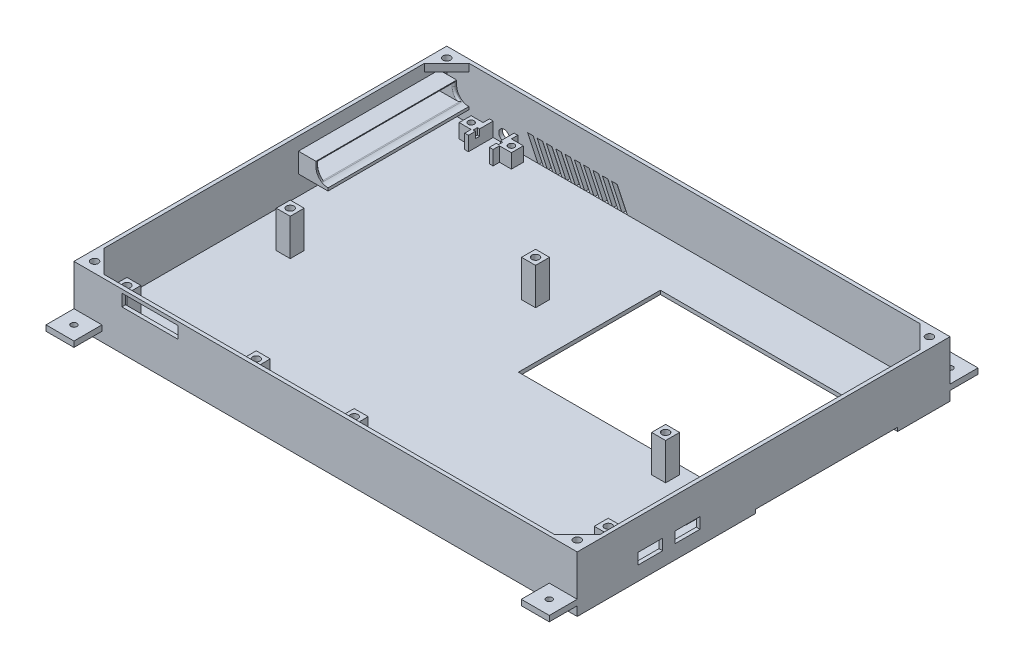
SolidWorks part; units mm, degrees
material "PLA"
ref_plane "Спереди" through (0, 0, 0) normal (0, 0, 1) x (1, 0, 0)
ref_plane "Сверху" through (0, 0, 0) normal (0, 1, 0) x (1, 0, 0)
ref_plane "Справа" through (0, 0, 0) normal (1, 0, 0) x (0, 0, -1)
sketch "Эскиз1" plane through (0, 0, 0) normal (0, 1, 0) x (1, 0, 0)
  line L1 (135, 100) -> (-135, 100)
  line L2 (135, 100) -> (135, -100)
  line L3 (135, -100) -> (-135, -100)
  line L4 (-135, 100) -> (-135, -100)
  line L5 (135, 100) -> (-135, -100) construction
  line L6 (135, -100) -> (-135, 100) construction
  point P0 (0, 0)
  dimension "D1" = 200
  dimension "D2" = 270
extrude "Бобышка-Вытянуть1" add sketch "Эскиз1" along normal blind 2
sketch "Эскиз2" plane through (0, 2, 0) normal (0, 1, 0) x (1, 0, 0)
  line L0 (133, 98) -> (-133, 98)
  line L1 (-133, 98) -> (-133, -98)
  line L2 (-133, -98) -> (-109.3, -98)
  line L3 (133, -98) -> (133, 98)
  line L4 (-135, 100) -> (-135, -100)
  line L5 (-135, -100) -> (135, -100)
  line L6 (135, -100) -> (135, 100)
  line L7 (135, 100) -> (-135, 100)
  line L8 (-135, 100) -> (-135, -100)
  line L9 (-135, -100) -> (-109.3, -100)
  line L10 (135, -100) -> (135, 100)
  line L11 (135, 100) -> (-135, 100)
  line L12 (-109.3, -98) -> (-109.3, -100)
  line L14 (-79.1, -98) -> (-79.1, -100)
  line L16 (-79.1, -98) -> (133, -98)
  line L17 (-79.1, -100) -> (135, -100)
  line L18 (-133, -98) -> (133, -98) construction
  line L20 (-135, -100) -> (135, -100) construction
  dimension "D3" = 25.7
  dimension "D4" = 55.9
  dimension "D1" = 0
  dimension "D2" = 2
extrude "Бобышка-Вытянуть2" add sketch "Эскиз2" along normal offset from surface (28 mm away) 7 offset beyond the face yes
sketch "Эскиз3" plane through (0, 2, 0) normal (0, 1, 0) x (1, 0, 0)
  line L1 (-109.3, -98) -> (-79.1, -98)
  line L2 (-109.3, -98) -> (-109.3, -100)
  line L3 (-109.3, -100) -> (-79.1, -100)
  line L4 (-79.1, -98) -> (-79.1, -100)
extrude "Бобышка-Вытянуть3" add sketch "Эскиз3" along normal blind 19.7
sketch "Эскиз4" plane through (-109.3, 0, 0) normal (1, 0, 0) x (0, 0, -1)
  line L0 (-100, 30) -> (-100, 21.7) construction
  line L1 (-98, 30) -> (-100, 30)
  line L2 (-98, 30) -> (-98, 28.1)
  line L3 (-98, 28.1) -> (-100, 28.1)
  line L4 (-100, 30) -> (-100, 28.1)
  dimension "D1" = 1.9
extrude "Бобышка-Вытянуть4" add sketch "Эскиз4" along normal up to surface (30.2 mm away) up to face at (-79.1, 25.85, 99)
sketch "Эскиз5" plane through (135, 0, 0) normal (1, 0, 0) x (0, 0, -1)
  line L0 (-100, 30) -> (-100, 0) construction
  line L1 (-54.15, 13.5) -> (-67.45, 13.5)
  line L2 (-54.15, 13.5) -> (-54.15, 7.6)
  line L3 (-54.15, 7.6) -> (-67.45, 7.6)
  line L4 (-67.45, 13.5) -> (-67.45, 7.6)
  line L5 (-54.15, 13.5) -> (-67.45, 7.6) construction
  line L6 (-54.15, 7.6) -> (-67.45, 13.5) construction
  line L7 (-34.15, 13.5) -> (-47.45, 13.5)
  line L8 (-34.15, 13.5) -> (-34.15, 7.6)
  line L9 (-34.15, 7.6) -> (-47.45, 7.6)
  line L10 (-47.45, 13.5) -> (-47.45, 7.6)
  line L11 (-34.15, 13.5) -> (-47.45, 7.6) construction
  line L12 (-34.15, 7.6) -> (-47.45, 13.5) construction
  line L13 (-100, 0) -> (100, 0) construction
  point P0 (-60.8, 10.55)
  point P5 (-40.8, 10.55)
  dimension "D1" = 13.3
  dimension "D2" = 5.9
  dimension "D3" = 6.7
  dimension "D4" = 32.55
  dimension "D5" = 13.5
extrude "Вырез-Вытянуть1" cut sketch "Эскиз5" against normal up to surface (2 mm away) up to face at (133, 16, 0)
sketch "Эскиз10" plane through (0, 2, 0) normal (0, 1, 0) x (1, 0, 0)
  line L0 (133, 98) -> (133, -98) construction
  line L1 (123.675, -22.825) -> (116.175, -22.825)
  line L2 (123.675, -22.825) -> (123.675, -30.325)
  line L3 (123.675, -30.325) -> (116.175, -30.325)
  line L4 (116.175, -22.825) -> (116.175, -30.325)
  line L5 (123.675, -22.825) -> (116.175, -30.325) construction
  line L6 (123.675, -30.325) -> (116.175, -22.825) construction
  line L7 (114.05, -54.9) -> (106.55, -54.9)
  line L8 (114.05, -54.9) -> (114.05, -62.4)
  line L9 (114.05, -62.4) -> (106.55, -62.4)
  line L10 (106.55, -54.9) -> (106.55, -62.4)
  line L11 (114.05, -54.9) -> (106.55, -62.4) construction
  line L12 (114.05, -62.4) -> (106.55, -54.9) construction
  line L13 (114.675, -87.875) -> (107.175, -87.875)
  line L14 (114.675, -87.875) -> (114.675, -95.375)
  line L15 (114.675, -95.375) -> (107.175, -95.375)
  line L16 (107.175, -87.875) -> (107.175, -95.375)
  line L17 (114.675, -87.875) -> (107.175, -95.375) construction
  line L18 (114.675, -95.375) -> (107.175, -87.875) construction
  line L19 (133, -98) -> (-133, -98) construction
  point P0 (119.925, -26.575)
  point P5 (110.3, -58.65)
  point P10 (110.925, -91.625)
  dimension "D1" = 13.075
  dimension "D2" = 71.425
  dimension "D3" = 22.7
  dimension "D4" = 39.35
  dimension "D5" = 22.075
  dimension "D6" = 6.375
  dimension "D7" = 7.5
extrude "Бобышка-Вытянуть6" add sketch "Эскиз10" along normal blind 6.9
sketch "Эскиз11" plane through (0, 2, 0) normal (0, 1, 0) x (1, 0, 0)
  line L1 (-45.3446, -84.35) -> (-52.8446, -84.35)
  line L2 (-45.3446, -84.35) -> (-45.3446, -91.85)
  line L3 (-45.3446, -91.85) -> (-52.8446, -91.85)
  line L4 (-52.8446, -84.35) -> (-52.8446, -91.85)
  line L5 (-45.3446, -84.35) -> (-52.8446, -91.85) construction
  line L6 (-45.3446, -91.85) -> (-52.8446, -84.35) construction
  line L7 (-17.6224, 30.2491) -> (-25.1224, 30.2491)
  line L8 (-17.6224, 30.2491) -> (-17.6224, 37.7491)
  line L9 (-17.6224, 37.7491) -> (-25.1224, 37.7491)
  line L10 (-25.1224, 30.2491) -> (-25.1224, 37.7491)
  line L11 (-17.6224, 30.2491) -> (-25.1224, 37.7491) construction
  line L12 (-17.6224, 37.7491) -> (-25.1224, 30.2491) construction
  line L13 (-114.1446, -92.4424) -> (-121.6446, -92.4424)
  line L14 (-114.1446, -92.4424) -> (-114.1446, -84.9424)
  line L15 (-114.1446, -84.9424) -> (-121.6446, -84.9424)
  line L16 (-121.6446, -92.4424) -> (-121.6446, -84.9424)
  line L17 (-114.1446, -92.4424) -> (-121.6446, -84.9424) construction
  line L18 (-114.1446, -84.9424) -> (-121.6446, -92.4424) construction
  line L19 (-106.25, -12.7324) -> (-113.75, -12.7324)
  line L20 (-106.25, -12.7324) -> (-106.25, -5.2324)
  line L21 (-106.25, -5.2324) -> (-113.75, -5.2324)
  line L22 (-113.75, -12.7324) -> (-113.75, -5.2324)
  line L23 (-106.25, -12.7324) -> (-113.75, -5.2324) construction
  line L24 (-106.25, -5.2324) -> (-113.75, -12.7324) construction
  line L25 (98.6279, -16.2195) -> (91.1279, -16.2195)
  line L26 (98.6279, -16.2195) -> (98.6279, -8.7195)
  line L27 (98.6279, -8.7195) -> (91.1279, -8.7195)
  line L28 (91.1279, -16.2195) -> (91.1279, -8.7195)
  line L29 (98.6279, -16.2195) -> (91.1279, -8.7195) construction
  line L30 (98.6279, -8.7195) -> (91.1279, -16.2195) construction
  line L31 (95.4554, -97.6196) -> (87.9554, -97.6196)
  line L32 (95.4554, -97.6196) -> (95.4554, -90.1196)
  line L33 (95.4554, -90.1196) -> (87.9554, -90.1196)
  line L34 (87.9554, -97.6196) -> (87.9554, -90.1196)
  line L35 (95.4554, -97.6196) -> (87.9554, -90.1196) construction
  line L36 (95.4554, -90.1196) -> (87.9554, -97.6196) construction
  line L37 (7.7554, -92.4285) -> (0.2554, -92.4285)
  line L38 (7.7554, -92.4285) -> (7.7554, -84.9285)
  line L39 (7.7554, -84.9285) -> (0.2554, -84.9285)
  line L40 (0.2554, -92.4285) -> (0.2554, -84.9285)
  line L41 (7.7554, -92.4285) -> (0.2554, -84.9285) construction
  line L42 (7.7554, -84.9285) -> (0.2554, -92.4285) construction
  line L44 (-133, 98) -> (133, 98) construction
  line L45 (-133, -98) -> (-133, 98) construction
  line L47 (133, -98) -> (-133, -98) construction
  line L48 (133, 98) -> (133, -98) construction
  point P0 (-49.0946, -88.1)
  point P5 (-21.3724, 33.9991)
  point P10 (-117.8946, -88.6924)
  point P15 (-110, -8.9824)
  point P20 (94.8779, -12.4695)
  point P25 (91.7054, -93.8696)
  point P30 (4.0054, -88.6785)
  dimension "D1" = 7.5
  dimension "D2" = 64.0009
  dimension "D3" = 111.6276
  dimension "D4" = 106.9824
  dimension "D5" = 23
  dimension "D6" = 9.3076
  dimension "D7" = 15.1054
  dimension "D8" = 9.3215
  dimension "D9" = 128.9946
  dimension "D10" = 9.9
  dimension "D11" = 83.9054
  dimension "D12" = 4.1304
  dimension "D13" = 41.2946
  dimension "D14" = 85.5305
  dimension "D15" = 38.1221
extrude "Бобышка-Вытянуть7" add sketch "Эскиз11" along normal blind 19.7
sketch "Эскиз12" plane through (0, 2, 0) normal (0, 1, 0) x (1, 0, 0)
  line L1 (135, 71.9) -> (7.7, 71.9)
  line L2 (135, 71.9) -> (135, -4.25)
  line L3 (135, -4.25) -> (7.7, -4.25)
  line L4 (7.7, 71.9) -> (7.7, -4.25)
  line L5 (-133, 98) -> (133, 98) construction
  line L6 (135, -100) -> (135, 100) construction
  dimension "D1" = 76.15
  dimension "D2" = 127.3
  dimension "D3" = 26.1
extrude "Вырез-Вытянуть2" cut sketch "Эскиз12" against normal through all
sketch "Эскиз14" plane through (0, 21.7, 0) normal (0, 1, 0) x (1, 0, 0)
  line L0 (-113.75, -5.2324) -> (-106.25, -12.7324) construction
  line L1 (-106.25, -5.2324) -> (-113.75, -12.7324) construction
  line L2 (-17.6224, 37.7491) -> (-25.1224, 30.2491) construction
  line L3 (-25.1224, 37.7491) -> (-17.6224, 30.2491) construction
  line L4 (-121.6446, -84.9424) -> (-114.1446, -92.4424) construction
  line L5 (-114.1446, -84.9424) -> (-121.6446, -92.4424) construction
  line L6 (-52.8446, -84.35) -> (-45.3446, -91.85) construction
  line L7 (-45.3446, -84.35) -> (-52.8446, -91.85) construction
  line L8 (0.2554, -84.9285) -> (7.7554, -92.4285) construction
  line L9 (7.7554, -84.9285) -> (0.2554, -92.4285) construction
  line L10 (95.4554, -90.1196) -> (87.9554, -97.6196) construction
  line L11 (95.4554, -90.1196) -> (87.9554, -90.1196) construction
  line L12 (95.4554, -90.1196) -> (95.4554, -97.6196) construction
  line L13 (95.4554, -97.6196) -> (87.9554, -97.6196) construction
  line L14 (87.9554, -90.1196) -> (87.9554, -97.6196) construction
  line L15 (95.4554, -97.6196) -> (87.9554, -90.1196) construction
  line L22 (98.6279, -8.7195) -> (91.1279, -16.2195) construction
  line L23 (98.6279, -16.2195) -> (91.1279, -8.7195) construction
  circle A0 centre (-21.3724, 33.9991) radius 2
  circle A1 centre (-110, -8.9824) radius 2
  circle A2 centre (-117.8946, -88.6924) radius 2
  circle A3 centre (-49.0946, -88.1) radius 2
  circle A4 centre (4.0054, -88.6785) radius 2
  circle A5 centre (91.7054, -93.8696) radius 2
  circle A6 centre (94.8779, -12.4695) radius 2
  dimension "D1" = 4
extrude "Вырез-Вытянуть4" cut sketch "Эскиз14" against normal blind 5
sketch "Эскиз15" plane through (0, 8.9, 0) normal (0, 1, 0) x (1, 0, 0)
  line L0 (123.675, -22.825) -> (116.175, -30.325) construction
  line L1 (116.175, -22.825) -> (123.675, -30.325) construction
  line L2 (106.55, -54.9) -> (114.05, -62.4) construction
  line L3 (114.05, -54.9) -> (106.55, -62.4) construction
  line L4 (107.175, -87.875) -> (114.675, -95.375) construction
  line L5 (114.675, -87.875) -> (107.175, -95.375) construction
  circle A0 centre (110.925, -91.625) radius 2
  circle A1 centre (110.3, -58.65) radius 2
  circle A2 centre (119.925, -26.575) radius 2
  dimension "D1" = 4
extrude "Вырез-Вытянуть5" cut sketch "Эскиз15" against normal blind 5
sketch "Эскиз16" plane through (0, 0, -100) normal (0, 0, -1) x (-1, 0, 0)
  line L0 (133, 23) -> (123.6, 23)
  line L1 (133, 30) -> (133, 2) construction
  line L2 (123.6, 23) -> (123.6, 20.4)
  line L3 (117.1, 13.9) -> (133, 13.9)
  line L4 (133, 13.9) -> (133, 23)
  line L5 (133, 2) -> (-133, 2) construction
  arc A0 (123.6, 20.4) -> (117.1, 13.9) centre (117.1, 20.4) cw
  dimension "D3" = 6.5
  dimension "D1" = 9.4
  dimension "D2" = 2.6
  dimension "D4" = 21
  dimension "D5" = 15.9
extrude "Бобышка-Вытянуть8" add sketch "Эскиз16" against normal blind 75.5 from offset 6.0824 offset against normal yes
sketch "Эскиз18" plane through (0, 0, -18.4176) normal (0, 0, 1) x (1, 0, 0)
  line L0 (-135, 22) -> (-123.6, 22)
  line L1 (-135, 30) -> (-135, 0) construction
  line L2 (-123.6, 23) -> (-123.6, 20.4) construction
  line L3 (-123.6, 22) -> (-123.6, 20.4)
  line L4 (-135, 22) -> (-135, 14.9)
  line L5 (-135, 14.9) -> (-120.5641, 14.9)
  line L6 (-133, 23) -> (-123.6, 23) construction
  line L7 (-117.1, 13.9) -> (-133, 13.9) construction
  arc A0 (-123.6, 20.4) -> (-117.1, 13.9) centre (-117.1, 20.4) ccw construction
  arc A1 (-123.6, 20.4) -> (-120.5641, 14.9) centre (-117.1, 20.4) ccw
  dimension "D1" = 1
  dimension "D2" = 1
extrude "Вырез-Вытянуть6" cut sketch "Эскиз18" against normal offset from surface (72.5 mm away) 1.5 from offset 1.5 up to face at (-126.3292, 18.5708, -93.9176) offset against normal yes
fillet "Скругление1" radius 1 6 edges at (-123.6, 21.2, -92.4176) (-123.6, 21.2, -19.9176) (-122.7906, 17.2589, -92.4176) (-120.5641, 14.9, -56.1676) (-122.7906, 17.2589, -19.9176) (-123.6, 22, -56.1676)
sketch "Эскиз19" plane through (0, 0, -18.4176) normal (0, 0, 1) x (1, 0, 0)
  line L0 (-133, 13.9) -> (-133, 12.4)
  line L1 (-133, 30) -> (-133, 2) construction
  line L2 (-133, 13.9) -> (-117.1, 13.9)
  line L3 (-117.1, 13.9) -> (-133, 13.9) construction
  line L4 (-117.1, 13.9) -> (-117.1, 12.4)
  line L5 (-117.1, 12.4) -> (-133, 12.4)
  dimension "D1" = 1.5
extrude "Бобышка-Вытянуть9" add sketch "Эскиз19" against normal up to surface (75.5 mm away) up to face at (-126.3292, 18.5708, -93.9176)
sketch "Эскиз20" plane through (0, 0, -100) normal (0, 0, -1) x (-1, 0, 0)
  line L0 (135, 30) -> (135, 0) construction
  line L1 (89.5705, 13.5) -> (86.5705, 13.5)
  line L3 (83.9, 1.5) -> (80.9, 1.5)
  line L5 (90.9, 13.5) -> (35.9, 1.5) construction
  line L6 (90.9, 1.5) -> (35.9, 13.5) construction
  line L7 (-135, 0) -> (135, 0) construction
  line L8 (35.9, 1.5) -> (41.5705, 13.5)
  line L9 (44.5705, 13.5) -> (38.9, 1.5)
  line L10 (40.9, 1.5) -> (46.5705, 13.5)
  line L11 (49.5705, 13.5) -> (43.9, 1.5)
  line L12 (45.9, 1.5) -> (51.5705, 13.5)
  line L13 (54.5705, 13.5) -> (48.9, 1.5)
  line L14 (50.9, 1.5) -> (56.5705, 13.5)
  line L15 (59.5705, 13.5) -> (53.9, 1.5)
  line L16 (55.9, 1.5) -> (61.5705, 13.5)
  line L17 (64.5705, 13.5) -> (58.9, 1.5)
  line L18 (60.9, 1.5) -> (66.5705, 13.5)
  line L19 (69.5705, 13.5) -> (63.9, 1.5)
  line L20 (65.9, 1.5) -> (71.5705, 13.5)
  line L21 (74.5705, 13.5) -> (68.9, 1.5)
  line L22 (70.9, 1.5) -> (76.5705, 13.5)
  line L23 (79.5705, 13.5) -> (73.9, 1.5)
  line L24 (75.9, 1.5) -> (81.5705, 13.5)
  line L25 (84.5705, 13.5) -> (78.9, 1.5)
  line L26 (80.9, 1.5) -> (86.5705, 13.5)
  line L27 (89.5705, 13.5) -> (83.9, 1.5)
  line L28 (44.5705, 13.5) -> (41.5705, 13.5)
  line L29 (38.9, 1.5) -> (35.9, 1.5)
  line L30 (43.9, 1.5) -> (40.9, 1.5)
  line L31 (49.5705, 13.5) -> (46.5705, 13.5)
  line L32 (54.5705, 13.5) -> (51.5705, 13.5)
  line L33 (48.9, 1.5) -> (45.9, 1.5)
  line L34 (53.9, 1.5) -> (50.9, 1.5)
  line L35 (59.5705, 13.5) -> (56.5705, 13.5)
  line L36 (58.9, 1.5) -> (55.9, 1.5)
  line L37 (64.5705, 13.5) -> (61.5705, 13.5)
  line L38 (63.9, 1.5) -> (60.9, 1.5)
  line L39 (69.5705, 13.5) -> (66.5705, 13.5)
  line L40 (68.9, 1.5) -> (65.9, 1.5)
  line L41 (74.5705, 13.5) -> (71.5705, 13.5)
  line L42 (73.9, 1.5) -> (70.9, 1.5)
  line L43 (79.5705, 13.5) -> (76.5705, 13.5)
  line L44 (78.9, 1.5) -> (75.9, 1.5)
  line L45 (84.5705, 13.5) -> (81.5705, 13.5)
  line L46 (35.9, 13.5) -> (35.9, 1.5) construction
  line L47 (90.9, 13.5) -> (90.9, 1.5) construction
  point P0 (63.4, 7.5)
  dimension "D1" = 71.6
  dimension "D2" = 1.5
  dimension "D3" = 12
  dimension "D4" = 55
  dimension "D5" = 3
  dimension "D8" = 2
  dimension "D9" = 64.707
  dimension "D6" = 10
extrude "Вырез-Вытянуть7" cut sketch "Эскиз20" against normal up to surface (2 mm away) up to face at (0, 16, -98)
sketch "Эскиз21" plane through (0, 0, -100) normal (0, 0, -1) x (-1, 0, 0)
  line L0 (135, 30) -> (135, 0) construction
  line L1 (-135, 0) -> (135, 0) construction
  circle A0 centre (102.2, 5.825) radius 2.9
  dimension "D1" = 5.8
  dimension "D2" = 32.8
  dimension "D3" = 5.825
extrude "Вырез-Вытянуть8" cut sketch "Эскиз21" against normal up to surface (2 mm away) up to face at (-57.1394, 8.5, -98)
sketch "Эскиз22" plane through (0, 2, 0) normal (0, 1, 0) x (1, 0, 0)
  line L0 (-133, 98) -> (-84.1363, 98) construction
  line L1 (-108.1, 98) -> (-110.1, 98)
  line L2 (-108.1, 98) -> (-108.1, 84.75)
  line L3 (-108.1, 84.75) -> (-110.1, 84.75)
  line L4 (-110.1, 98) -> (-110.1, 84.75)
  line L5 (-133, -98) -> (-133, 98) construction
  line L7 (-94.9, 98) -> (-96.9, 98)
  line L8 (-94.9, 98) -> (-94.9, 84.75)
  line L9 (-94.9, 84.75) -> (-96.9, 84.75)
  line L10 (-96.9, 98) -> (-96.9, 84.75)
  dimension "D1" = 24.9
  dimension "D2" = 13.25
  dimension "D3" = 2
  dimension "D4" = 36.1
extrude "Бобышка-Вытянуть10" add sketch "Эскиз22" along normal blind 7.65
sketch "Эскиз23" plane through (0, 9.65, 0) normal (0, 1, 0) x (1, 0, 0)
  line L0 (-108.1, 84.75) -> (-108.1, 98) construction
  line L1 (-108.1, 90.7) -> (-109.3, 90.7)
  line L2 (-108.1, 90.7) -> (-108.1, 88.5)
  line L3 (-108.1, 88.5) -> (-109.3, 88.5)
  line L4 (-109.3, 90.7) -> (-109.3, 88.5)
  line L5 (-96.9, 98) -> (-96.9, 84.75) construction
  line L6 (-96.9, 90.7) -> (-95.7, 90.7)
  line L7 (-96.9, 90.7) -> (-96.9, 88.5)
  line L8 (-96.9, 88.5) -> (-95.7, 88.5)
  line L9 (-95.7, 90.7) -> (-95.7, 88.5)
  line L10 (-110.1, 84.75) -> (-108.1, 84.75) construction
  dimension "D1" = 2.2
  dimension "D2" = 1.2
  dimension "D3" = 5.95
extrude "Вырез-Вытянуть9" cut sketch "Эскиз23" against normal blind 3.45
sketch "Эскиз24" plane through (0, 2, 0) normal (0, 1, 0) x (1, 0, 0)
  line L0 (-108.6, 91.375) -> (-97.4, 91.375) construction
  line L3 (-102.5, 91.875) -> (-102.5, 50091.875) construction
  line L4 (-108.1, 84.75) -> (-108.1, 98) construction
  line L5 (-108.1, 98) -> (-96.9, 98) construction
  line L6 (-110.1, 98) -> (-110.1, 84.75) construction
  line L7 (-116.5, 94.575) -> (-110.1, 94.575)
  line L8 (-116.5, 94.575) -> (-116.5, 88.175)
  line L9 (-116.5, 88.175) -> (-110.1, 88.175)
  line L10 (-110.1, 94.575) -> (-110.1, 88.175)
  line L11 (-116.5, 94.575) -> (-110.1, 88.175) construction
  line L12 (-116.5, 88.175) -> (-110.1, 94.575) construction
  line L13 (-88.5, 88.175) -> (-94.9, 88.175)
  line L14 (-94.9, 94.575) -> (-94.9, 88.175)
  line L15 (-88.5, 94.575) -> (-94.9, 94.575)
  line L16 (-88.5, 94.575) -> (-88.5, 88.175)
  circle A0 centre (-113.3, 91.375) radius 1.7 construction
  point P3 (-108.1, 91.375)
  point P8 (-102.5, 98)
  point P10 (-113.3, 91.375)
  dimension "D1" = 3.4
  dimension "D2" = 1.5
extrude "Бобышка-Вытянуть11" add sketch "Эскиз24" along normal up to surface (7.65 mm away) up to face at (-108.9, 9.65, -90.4875)
sketch "Эскиз25" plane through (0, 9.65, 0) normal (0, 1, 0) x (1, 0, 0)
  line L0 (-116.5, 94.575) -> (-110.1, 88.175) construction
  line L1 (-110.1, 94.575) -> (-116.5, 88.175) construction
  line L2 (-94.9, 94.575) -> (-88.5, 88.175) construction
  line L3 (-88.5, 94.575) -> (-94.9, 88.175) construction
  circle A0 centre (-113.3, 91.375) radius 1.65
  circle A1 centre (-91.7, 91.375) radius 1.65
  dimension "D1" = 3.3
extrude "Вырез-Вытянуть10" cut sketch "Эскиз25" against normal blind 3
sketch "Эскиз26" plane through (0, 30, 0) normal (0, 1, 0) x (1, 0, 0)
  line L0 (0, 0) -> (0, 50000) construction
  line L1 (0, 0) -> (-50000, 0) construction
  line L2 (121, 98) -> (133, 98)
  line L3 (-36.1363, 98) -> (133, 98) construction
  line L4 (133, 98) -> (133, 86)
  line L5 (133, 98) -> (133, -98) construction
  line L6 (133, 86) -> (121, 98)
  line L7 (133, 98) -> (127, 92) construction
  line L8 (133, -98) -> (133, -86)
  line L9 (121, -98) -> (133, -98)
  line L10 (133, -86) -> (121, -98)
  line L11 (-121, -98) -> (-133, -98)
  line L12 (-133, -86) -> (-121, -98)
  line L13 (-133, -98) -> (-133, -86)
  line L14 (-133, 98) -> (-133, 86)
  line L15 (-121, 98) -> (-133, 98)
  line L16 (-133, 86) -> (-121, 98)
  circle A0 centre (129.5102, 94.5102) radius 2.05 construction
  dimension "D1" = 4.1
  dimension "D3" = 1.5
  dimension "D4" = 1.4398
  dimension "D2" = 12
extrude "Бобышка-Вытянуть12" add sketch "Эскиз26" against normal blind 4
sketch "Эскиз27" plane through (0, 30, 0) normal (0, 1, 0) x (1, 0, 0)
  line L0 (0, 0) -> (0, 50000) construction
  line L1 (0, 0) -> (-50000, 0) construction
  line L2 (135, 100) -> (127, 92) construction
  line L3 (121, 98) -> (133, 86) construction
  circle A0 centre (129.4749, 94.4749) radius 2
  circle A1 centre (129.4749, -94.4749) radius 2
  circle A2 centre (-129.4749, -94.4749) radius 2
  circle A3 centre (-129.4749, 94.4749) radius 2
  dimension "D1" = 4
  dimension "D2" = 1.5
extrude "Вырез-Вытянуть11" cut sketch "Эскиз27" against normal up to surface (4 mm away) up to face at (129, 26, -94)
sketch "Эскиз28" plane through (0, 0, -100) normal (0, 0, -1) x (-1, 0, 0)
  line L0 (-135, 30) -> (-135, 0) construction
  line L1 (-135, 5) -> (-120, 5)
  line L2 (-135, 5) -> (-135, 8)
  line L3 (-135, 8) -> (-120, 8)
  line L4 (-120, 5) -> (-120, 8)
  line L5 (-135, 0) -> (135, 0) construction
  point P5 (0, 0)
  point P6 (-135, 4.7301)
  dimension "D1" = 3
  dimension "D2" = 15
  dimension "D3" = 5
extrude "Бобышка-Вытянуть13" add sketch "Эскиз28" along normal blind 15
sketch "Эскиз29" plane through (0, 8, 0) normal (0, 1, 0) x (1, 0, 0)
  line L0 (120, 115) -> (135, 100) construction
  line L1 (135, 115) -> (120, 100) construction
  circle A0 centre (127.5, 107.5) radius 1.6
  dimension "D1" = 3.2
extrude "Вырез-Вытянуть12" cut sketch "Эскиз29" against normal through all
mirror "Зеркальное отражение1" about plane through (0, 0, 0) normal (0, 0, 1) of "Вырез-Вытянуть12", "Бобышка-Вытянуть13"
mirror "Зеркальное отражение2" about plane through (0, 0, 0) normal (1, 0, 0) of "Зеркальное отражение1"
